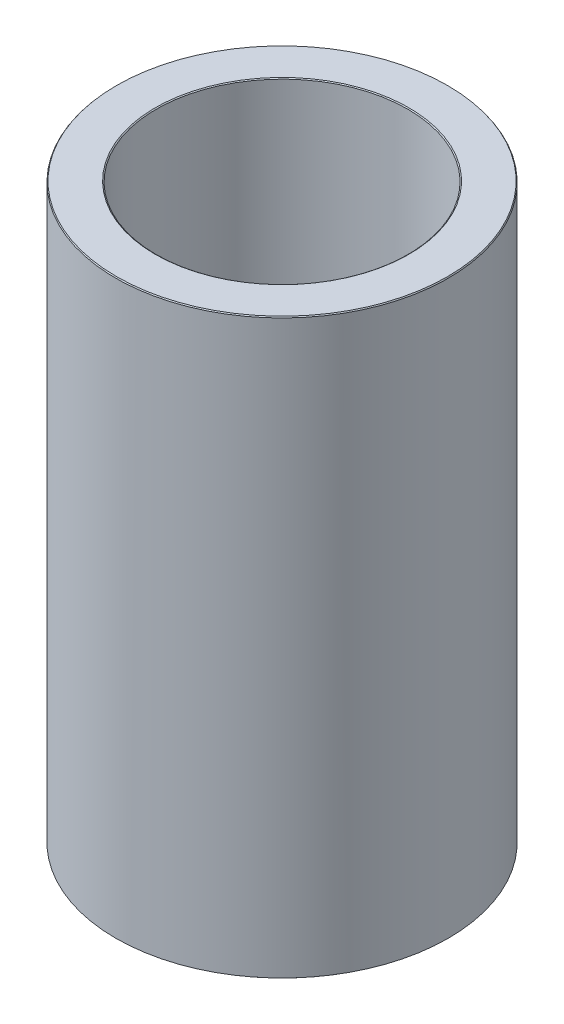
SolidWorks part; units mm, degrees
ref_plane "Front Plane" through (0, 0, 0) normal (0, 0, 1) x (1, 0, 0)
ref_plane "Top Plane" through (0, 0, 0) normal (0, 1, 0) x (1, 0, 0)
ref_plane "Right Plane" through (0, 0, 0) normal (1, 0, 0) x (0, 0, -1)
sketch "Sketch1" plane through (0, 0, 0) normal (0, 1, 0) x (1, 0, 0)
  circle A0 centre (0, 0) radius 57.5
  dimension "SLEEVE_OD" = 115
extrude "Boss-Extrude1" add sketch "Sketch1" along normal blind 198.3043
sketch "Sketch2" plane through (0, 0, 0) normal (0, 1, 0) x (1, 0, 0)
  circle A0 centre (0, 0) radius 43.534
  dimension "BORE_D" = 87.0679
extrude "Cut-Extrude1" cut sketch "Sketch2" along normal through all
chamfer "Chamfer1" distance 0.3582 angle 35.356 4 edges at (0, 198.3043, 43.534) (0, 0, 43.534) (0, 0, 57.5) (0, 198.3043, 57.5) first distance on face at (0, 198.3043, 43.534) first distance on face at (0, 0, 43.534) first distance on face at (0, 198.3043, 57.5)
